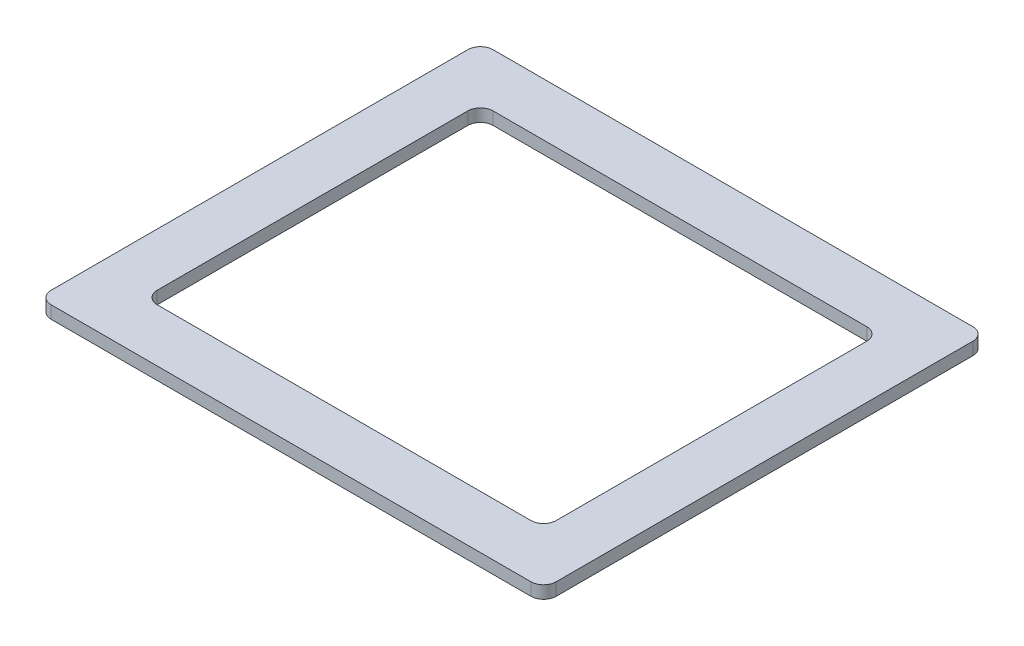
SolidWorks part; units mm, degrees
ref_plane "Front Plane" through (0, 0, 0) normal (0, 0, 1) x (1, 0, 0)
ref_plane "Top Plane" through (0, 0, 0) normal (0, 1, 0) x (1, 0, 0)
ref_plane "Right Plane" through (0, 0, 0) normal (1, 0, 0) x (0, 0, -1)
sketch "Sketch1" plane through (0, 0, 0) normal (0, 1, 0) x (1, 0, 0)
  line L1 (-200, -175) -> (200, -175)
  line L2 (-200, -175) -> (-200, 175)
  line L3 (-200, 175) -> (200, 175)
  line L4 (200, -175) -> (200, 175)
  line L5 (-200, -175) -> (200, 175) construction
  line L6 (-200, 175) -> (200, -175) construction
  point P0 (0, 0)
  dimension "D1" = 400
  dimension "D2" = 350
extrude "Boss-Extrude1" add sketch "Sketch1" along normal blind 10
sketch "Sketch2" plane through (0, 10, 0) normal (0, 1, 0) x (1, 0, 0)
  line L0 (-200, 175) -> (-200, -175) construction
  line L1 (-158, -133) -> (158, -133)
  line L2 (-158, -133) -> (-158, 133)
  line L3 (-158, 133) -> (158, 133)
  line L4 (158, -133) -> (158, 133)
  line L5 (-158, -133) -> (158, 133) construction
  line L6 (-158, 133) -> (158, -133) construction
  line L7 (200, 175) -> (-200, 175) construction
  point P0 (0, 0)
  dimension "D1" = 42
  dimension "D2" = 42
extrude "Cut-Extrude1" cut sketch "Sketch2" against normal through all
fillet "Fillet1" radius 10 8 edges at (-158, 5, -133) (200, 5, -175) (-158, 5, 133) (158, 5, 133) (200, 5, 175) (158, 5, -133) (-200, 5, -175) (-200, 5, 175)
